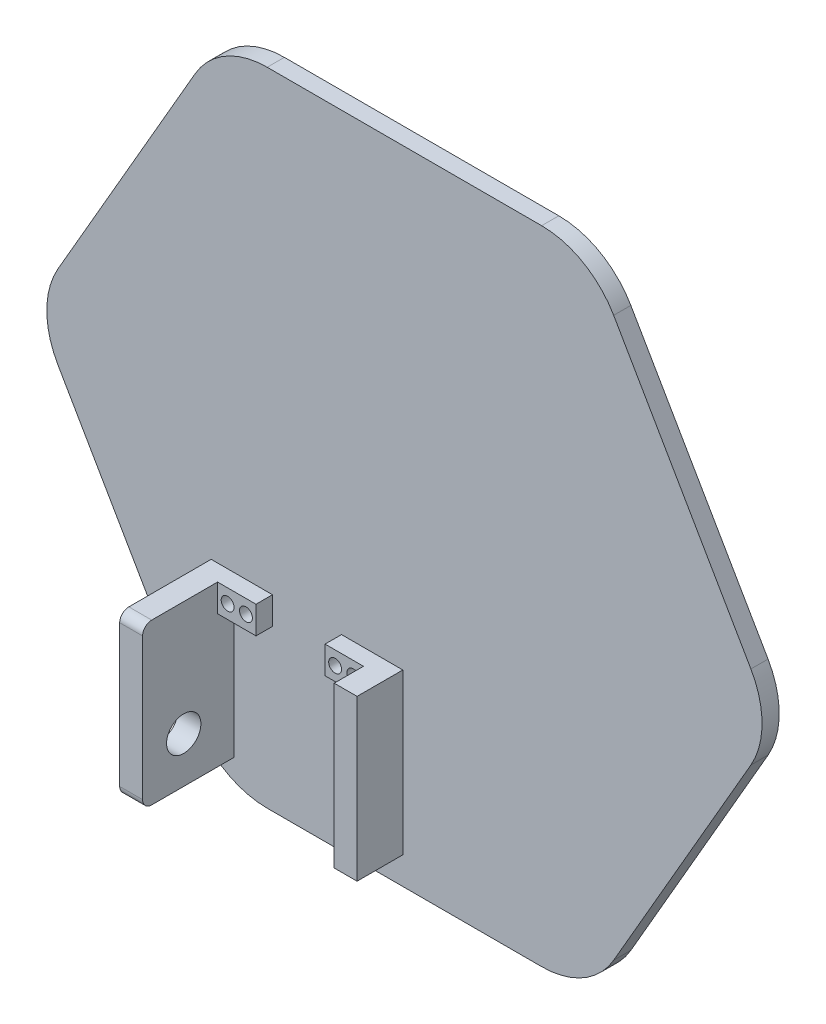
SolidWorks part; units mm, degrees
ref_plane "Front Plane" through (0, 0, 0) normal (0, 0, 1) x (1, 0, 0)
ref_plane "Top Plane" through (0, 0, 0) normal (0, 1, 0) x (1, 0, 0)
ref_plane "Right Plane" through (0, 0, 0) normal (1, 0, 0) x (0, 0, -1)
sketch "Sketch2" plane through (0, 0, 0) normal (0, 0, 1) x (1, 0, 0)
  line L1 (96.2019, 11.5481) -> (58.1019, 77.5392)
  line L2 (38.1, 89.0873) -> (-38.1, 89.0873)
  line L3 (-58.1019, 77.5392) -> (-96.2019, 11.5481)
  line L4 (-96.2019, -11.5481) -> (-58.1019, -77.5392)
  line L5 (-38.1, -89.0873) -> (38.1, -89.0873)
  line L6 (58.1019, -77.5392) -> (96.2019, -11.5481)
  circle A0 centre (0, 0) radius 89.0873 construction
  arc A1 (58.1019, 77.5392) -> (38.1, 89.0873) centre (38.1, 65.9911) ccw
  arc A2 (96.2019, 11.5481) -> (96.2019, -11.5481) centre (76.2, 0) cw
  arc A3 (38.1, -89.0873) -> (58.1019, -77.5392) centre (38.1, -65.9911) ccw
  arc A4 (-58.1019, -77.5392) -> (-38.1, -89.0873) centre (-38.1, -65.9911) ccw
  arc A5 (-96.2019, 11.5481) -> (-96.2019, -11.5481) centre (-76.2, 0) ccw
  arc A6 (-38.1, 89.0873) -> (-58.1019, 77.5392) centre (-38.1, 65.9911) ccw
  dimension "D1" = 76.2
extrude "Boss-Extrude1" add sketch "Sketch2" along normal blind 4.7625
sketch "Sketch4" plane through (0, 0, 4.7625) normal (0, 0, 1) x (1, 0, 0)
  line L0 (-38.1, -89.0873) -> (38.1, -89.0873) construction
  line L1 (-53.6569, -81.4673) -> (-47.3069, -81.4673)
  line L2 (-53.6569, -81.4673) -> (-53.6569, -37.0173)
  line L3 (-53.6569, -37.0173) -> (-47.3069, -37.0173)
  line L4 (-47.3069, -81.4673) -> (-47.3069, -37.0173)
  point P17 (0, 0)
  dimension "D1" = 6.35
  dimension "D2" = 44.45
  dimension "D3" = 7.62
  dimension "D4" = 4.445
extrude "Boss-Extrude3" add sketch "Sketch4" along normal blind 25.4
sketch "Sketch5" plane through (0, 0, 4.7625) normal (0, 0, 1) x (1, 0, 0)
  line L1 (-6.7975, -81.4673) -> (-0.4475, -81.4673)
  line L2 (-6.7975, -81.4673) -> (-6.7975, -37.0173)
  line L3 (-6.7975, -37.0173) -> (-0.4475, -37.0173)
  line L4 (-0.4475, -81.4673) -> (-0.4475, -37.0173)
  line L6 (-53.6569, -81.4673) -> (-47.3069, -81.4673) construction
  point P19 (0, 0)
  dimension "D1" = 6.35
extrude "Boss-Extrude6" add sketch "Sketch5" along normal blind 12.7
sketch "Sketch6" plane through (0, 0, 4.7625) normal (0, 0, 1) x (1, 0, 0)
  line L0 (-17.4655, -37.0173) -> (-6.7975, -37.0173)
  line L1 (-47.3069, -37.0173) -> (-36.6389, -37.0173)
  line L2 (-47.3069, -37.0173) -> (-47.3069, -44.6373)
  line L3 (-47.3069, -44.6373) -> (-36.6389, -44.6373)
  line L4 (-36.6389, -37.0173) -> (-36.6389, -44.6373)
  line L5 (-17.4655, -37.0173) -> (-17.4655, -44.6373)
  line L6 (-17.4655, -44.6373) -> (-6.7975, -44.6373)
  line L7 (-6.7975, -37.0173) -> (-6.7975, -44.6373)
  line L8 (-6.7975, -37.0173) -> (-6.7975, -81.4673) construction
  line L9 (-0.4475, -37.0173) -> (-6.7975, -37.0173) construction
  line L10 (-0.4475, -81.4673) -> (-0.4475, -37.0173) construction
  line L12 (-53.6569, -37.0173) -> (-53.6569, -81.4673) construction
  point P16 (0, 0)
  dimension "D1" = 7.62
  dimension "D2" = 17.018
  dimension "D3" = 7.62
  dimension "D4" = 17.018
extrude "Boss-Extrude5" add sketch "Sketch6" along normal blind 4.572
sketch "Sketch7" plane through (0, 0, 9.3345) normal (0, 0, 1) x (1, 0, 0)
  line L0 (-47.3069, -44.6373) -> (-36.6389, -44.6373) construction
  line L1 (-36.6389, -44.6373) -> (-36.6389, -37.0173) construction
  line L2 (-17.4655, -44.6373) -> (-6.7975, -44.6373) construction
  line L3 (-17.4655, -37.0173) -> (-17.4655, -44.6373) construction
  circle A0 centre (-44.5129, -40.8273) radius 1.7907
  circle A1 centre (-39.4329, -40.8273) radius 1.7907
  circle A2 centre (-14.6715, -40.8273) radius 1.7907
  circle A3 centre (-9.5915, -40.8273) radius 1.7907
  dimension "D1" = 3.5814
  dimension "D2" = 3.81
  dimension "D8" = 3.5814
  dimension "D9" = 3.5814
  dimension "D10" = 3.5814
  dimension "D3" = 5.08
  dimension "D4" = 2.794
  dimension "D5" = 3.81
  dimension "D6" = 2.794
  dimension "D7" = 5.08
extrude "Cut-Extrude1" cut sketch "Sketch7" against normal blind 6.731
sketch "Sketch9" plane through (-53.6569, 0, 0) normal (-1, 0, 0) x (0, 0, 1)
  line L0 (4.7625, -37.0173) -> (4.7625, -81.4673) construction
  line L1 (30.1625, -81.4673) -> (4.7625, -81.4673) construction
  circle A0 centre (7.5311, -68.7673) radius 2.286
  dimension "D1" = 4.572
  dimension "D2" = 2.7686
  dimension "D3" = 12.7
sketch "Sketch10" plane through (-53.6569, 0, 0) normal (-1, 0, 0) x (0, 0, 1)
  line L0 (30.1625, -81.4673) -> (4.7625, -81.4673) construction
  circle A0 centre (18.7325, -68.7673) radius 4.7625
  dimension "D1" = 9.525
  dimension "D2" = 11.2014
  dimension "D3" = 12.7
extrude "Cut-Extrude3" cut sketch "Sketch9" against normal blind 2.54
extrude "Cut-Extrude4" cut sketch "Sketch10" against normal up to surface (6.35 mm away) up to face at (-47.3069, -54.374, 14.7532)
fillet "Fillet2" radius 2.54 2 edges at (-50.4819, -37.0173, 30.1625) (-50.4819, -81.4673, 30.1625)
sketch3d "3DSketch1"
  line L0 (0, 0, 0) -> (0, 0, 50000) construction
